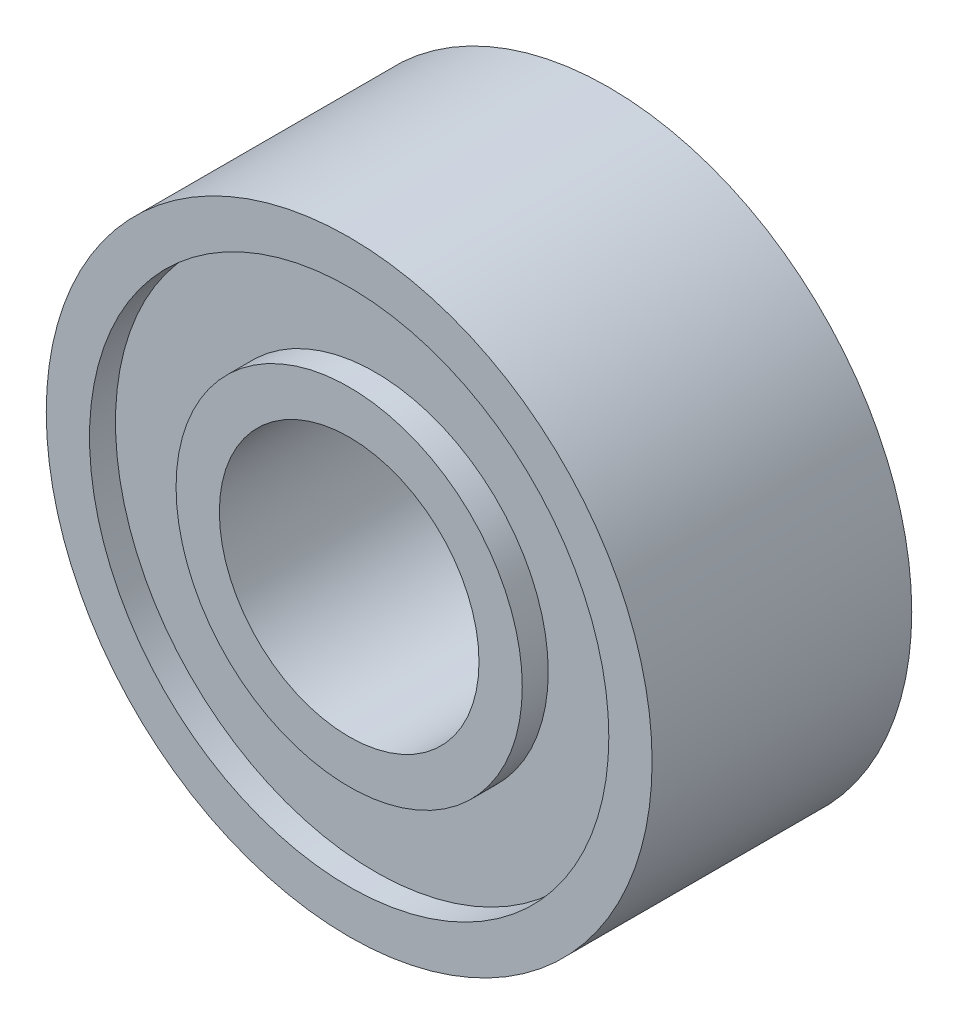
SolidWorks part; units mm, degrees
ref_plane "Front Plane" through (0, 0, 0) normal (0, 0, 1) x (1, 0, 0)
ref_plane "Top Plane" through (0, 0, 0) normal (0, 1, 0) x (1, 0, 0)
ref_plane "Right Plane" through (0, 0, 0) normal (1, 0, 0) x (0, 0, -1)
sketch "Sketch1" plane through (0, 0, 0) normal (0, 0, 1) x (1, 0, 0)
  circle A0 centre (0, 0) radius 1.5
  circle A1 centre (0, 0) radius 3.5
extrude "Boss-Extrude1" add sketch "Sketch1" along normal blind 3
sketch "Sketch2" plane through (0, 0, 3) normal (0, 0, 1) x (1, 0, 0)
  circle A0 centre (0, 0) radius 2
  circle A1 centre (0, 0) radius 3
extrude "Cut-Extrude1" cut sketch "Sketch2" against normal blind 0.3
extrude "Cut-Extrude2" cut sketch "Sketch2<2>" along normal blind 0.3 from surface starting at face at (3.5, 0, 0)
sketch "Sketch2<2>" plane through (0, 0, 3) normal (0, 0, 1) x (1, 0, 0) same geometry as "Sketch2"
